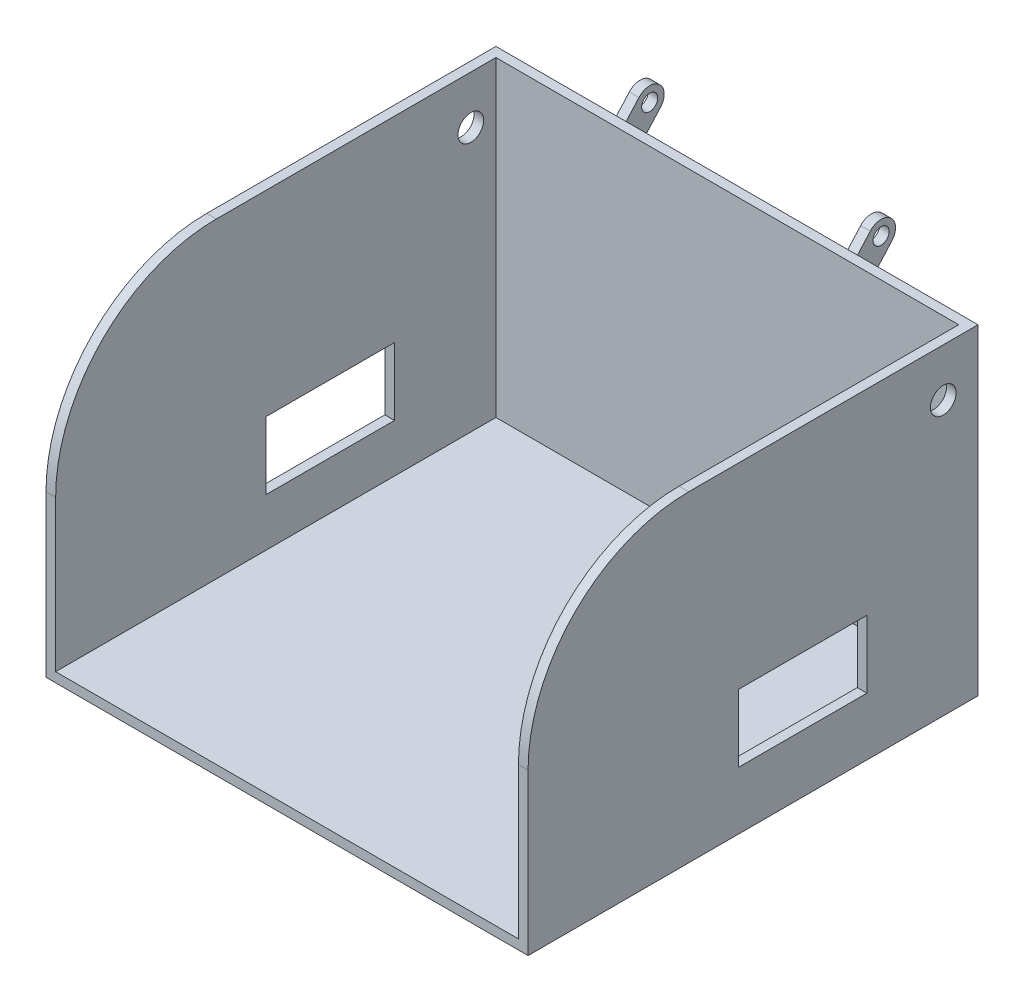
SolidWorks part; units mm, degrees
material "PLA"
ref_plane "Front Plane" through (0, 0, 0) normal (0, 0, 1) x (1, 0, 0)
ref_plane "Top Plane" through (0, 0, 0) normal (0, 1, 0) x (1, 0, 0)
ref_plane "Right Plane" through (0, 0, 0) normal (1, 0, 0) x (0, 0, -1)
sketch "Sketch1" plane through (0, 0, 0) normal (1, 0, 0) x (0, 0, -1)
  line L0 (0, 0) -> (-140, 0)
  line L1 (-140, 0) -> (-140, 50)
  line L2 (-90, 100) -> (0, 100)
  line L3 (0, 100) -> (0, 0)
  arc A0 (-140, 50) -> (-90, 100) centre (-90, 50) cw
  dimension "D1" = 140
  dimension "D2" = 100
  dimension "D3" = 50
extrude "Boss-Extrude1" add sketch "Sketch1" along normal blind 150 contours A0 L2 L3 L0 L1
sketch "Sketch2" plane through (0, 100, 0) normal (0, 1, 0) x (1, 0, 0)
  line L0 (150, 0) -> (0, 0) construction
  line L1 (3, -3) -> (147, -3)
  line L2 (3, -3) -> (3, -145)
  line L3 (3, -145) -> (147, -145)
  line L4 (147, -3) -> (147, -145)
  line L5 (150, -90) -> (150, 0) construction
  line L6 (0, -90) -> (0, 0) construction
  line L8 (150, -140) -> (0, -140) construction
  dimension "D1" = 3
  dimension "D2" = 3
  dimension "D3" = 3
  dimension "D4" = 5
extrude "Cut-Extrude1" cut sketch "Sketch2" against normal offset from surface (97 mm away) 3 up to face at (75, 0, 70)
ref_plane "Plane1" through (75, 0, 0) normal (1, 0, 0) x (0, 0, -1)
ref_plane "Plane2" through (111, 0, 0) normal (1, 0, 0) x (0, 0, -1)
ref_plane "Plane3" through (39, 0, 0) normal (1, 0, 0) x (0, 0, -1)
sketch "Sketch3" plane through (111, 0, 0) normal (1, 0, 0) x (0, 0, -1)
  line L0 (0, 100) -> (0, 86.4837)
  line L1 (0, 86.4837) -> (10.7098, 98.4837)
  line L2 (3.9952, 104.4764) -> (0, 100)
  arc A0 (10.7098, 98.4837) -> (3.9952, 104.4764) centre (7.3525, 101.4801) ccw
  circle A1 centre (7.3525, 101.4801) radius 2.5
  dimension "D1" = 2
  dimension "D2" = 5
  dimension "D3" = 6
  dimension "D4" = 12
extrude "Boss-Extrude2" add sketch "Sketch3" along normal mid plane 3
mirror "Mirror1" about plane through (75, 0, 0) normal (1, 0, 0) of "Boss-Extrude2"
sketch "Sketch4" plane through (150, 0, 0) normal (1, 0, 0) x (0, 0, -1)
  line L0 (-10.8107, 85.0634) -> (-67.3793, 28.4949) construction
  line L1 (-74.5612, 38.9949) -> (-74.5612, 17.9949)
  line L2 (-74.5612, 17.9949) -> (-34.5612, 17.9949)
  line L3 (0, 0) -> (-140, 0) construction
  line L4 (-34.5612, 17.9949) -> (-34.5612, 38.9949)
  line L5 (-34.5612, 38.9949) -> (-74.5612, 38.9949)
  circle A0 centre (-67.3793, 28.4949) radius 2.5
  circle A1 centre (-10.8107, 85.0634) radius 4
  point P8 (-74.5612, 28.4949)
  dimension "D4" = 8
  dimension "D5" = 5
  dimension "D1" = 80
  dimension "D2" = 45
  dimension "D3" = 40
  dimension "D6" = 21
extrude "Cut-Extrude2" cut sketch "Sketch4" against normal up to next contours A0 | A1 | L4 L5 A0 L1 L2 region at (150, 28.4949, 54.2544) region at (150, 28.4949, 67.3793) region at (150, 85.0634, 10.8107)
mirror "Mirror2" about plane through (75, 0, 0) normal (1, 0, 0) of "Cut-Extrude2"
equation "\"forward_length\"= 130"
equation "\"height\"= 100"
equation "\"eslabon_AB\"=80"
